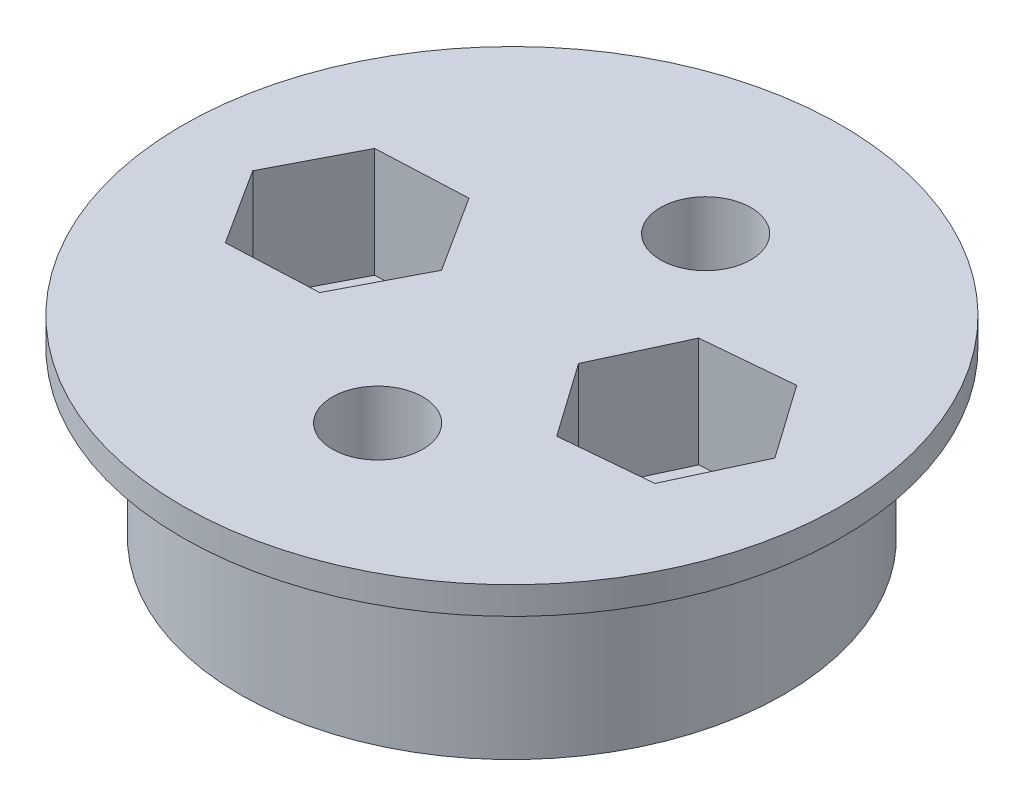
SolidWorks part; units mm, degrees
ref_plane "Front Plane" through (0, 0, 0) normal (0, 0, 1) x (1, 0, 0)
ref_plane "Top Plane" through (0, 0, 0) normal (0, 1, 0) x (1, 0, 0)
ref_plane "Right Plane" through (0, 0, 0) normal (1, 0, 0) x (0, 0, -1)
sketch "Sketch1" plane through (0, 0, 0) normal (0, 1, 0) x (1, 0, 0)
  line L0 (-3.8733, 1.211) -> (-3.8733, 6.8848) construction
  line L1 (-3.8733, 6.8848) -> (-3.8733, -5.3142) construction
  line L2 (-3.8733, 1.211) -> (17.1416, 1.211) construction
  line L3 (-3.8733, 1.211) -> (-18.1978, 1.211) construction
  line L4 (-1.8733, 1.211) -> (-1.8733, 13.3485) construction
  line L5 (-1.8733, 13.3485) -> (-1.8733, -12.0677) construction
  line L6 (0.1267, 1.211) -> (0.1267, 13.7037) construction
  line L7 (0.1267, 13.7037) -> (0.1267, -12.3834) construction
  line L8 (-0.9304, 13.3485) -> (-0.9304, -11.2019) construction
  line L10 (-6.1001, -1.5613) -> (-4.5858, 1.3605)
  line L11 (-4.5858, 1.3605) -> (-6.3591, 4.1328)
  line L12 (-6.3591, 4.1328) -> (-9.6466, 3.9833)
  line L13 (-9.6466, 3.9833) -> (-11.1608, 1.0615)
  line L14 (-11.1608, 1.0615) -> (-9.3876, -1.7108)
  line L15 (-9.3876, -1.7108) -> (-6.1001, -1.5613)
  line L17 (6.0218, -1.4794) -> (7.4042, 1.507)
  line L18 (7.4042, 1.507) -> (5.5091, 4.1975)
  line L19 (5.5091, 4.1975) -> (2.2315, 3.9014)
  line L20 (2.2315, 3.9014) -> (0.8491, 0.915)
  line L21 (0.8491, 0.915) -> (2.7443, -1.7755)
  line L22 (2.7443, -1.7755) -> (6.0218, -1.4794)
  circle A0 centre (-1.8733, 1.211) radius 9.9
  circle A2 centre (-0.9304, 7.3205) radius 1.65
  circle A4 centre (-0.9304, -4.6216) radius 1.65
  circle A8 centre (-1.8733, 1.211) radius 12
  circle A10 centre (-7.8733, 1.211) radius 1.65
  circle A11 centre (4.1267, 1.211) radius 1.65
  circle A12 centre (-7.8733, 1.211) radius 2.85 construction
  circle A13 centre (4.1267, 1.211) radius 2.85 construction
  dimension "D1" = 19.8
  dimension "D4" = 5.7
  dimension "D5" = 3.3
  dimension "D6" = 5.7
  dimension "D7" = 3.3
  dimension "D11" = 24
  dimension "D13" = 3.3
  dimension "D14" = 3.3
  dimension "D2" = 2
  dimension "D3" = 2
  dimension "D15" = 6
  dimension "D16" = 6
extrude "Boss-Extrude1" add sketch "Sketch1" against normal blind 7 contours A0
extrude "Boss-Extrude2" add sketch "Sketch1<3>" against normal blind 1 contours A8
sketch "Sketch1<3>" plane through (0, 0, 0) normal (0, 1, 0) x (1, 0, 0) same geometry as "Sketch1"
extrude "Cut-Extrude1" cut sketch "Sketch1<4>" against normal blind 11 contours A10 | A4 | A2 | A11
sketch "Sketch1<4>" plane through (0, 0, 0) normal (0, 1, 0) x (1, 0, 0) same geometry as "Sketch1"
extrude "Cut-Extrude2" cut sketch "Sketch1<5>" against normal blind 4 contours L12 L13 L14 L15 L10 L11 | L20 L21 L22 L17 L18 L19
sketch "Sketch1<5>" plane through (0, 0, 0) normal (0, 1, 0) x (1, 0, 0) same geometry as "Sketch1"
